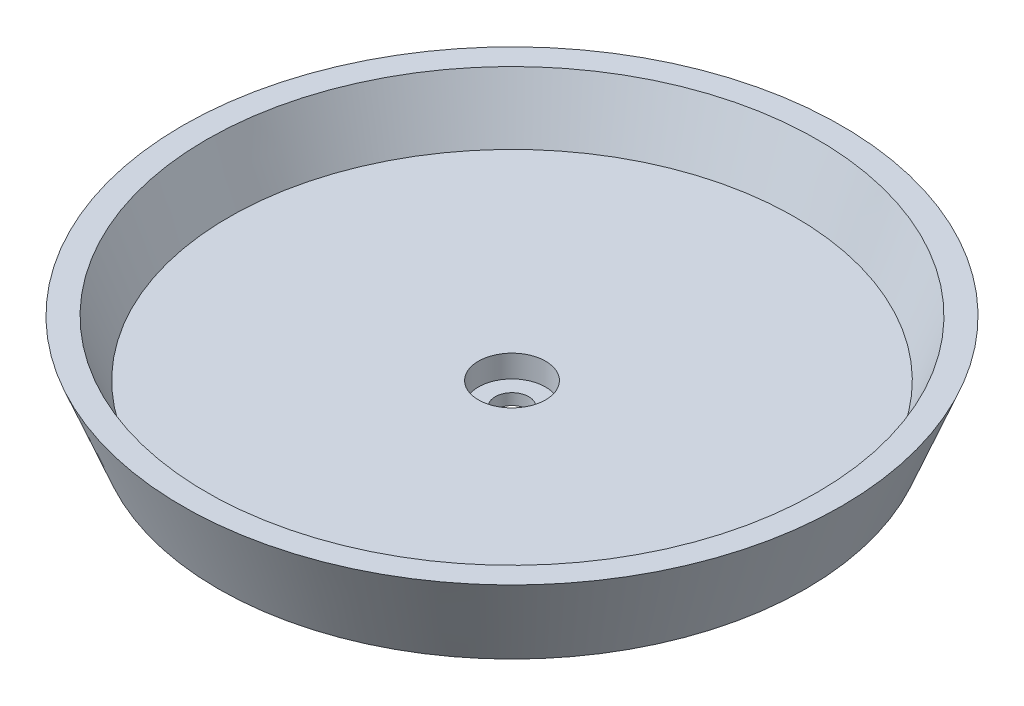
SolidWorks part; units mm, degrees
ref_plane "前视基准面" through (0, 0, 0) normal (0, 0, 1) x (1, 0, 0)
ref_plane "上视基准面" through (0, 0, 0) normal (0, 1, 0) x (1, 0, 0)
ref_plane "右视基准面" through (0, 0, 0) normal (1, 0, 0) x (0, 0, -1)
sketch "草图1" plane through (0, 0, 0) normal (0, 0, 1) x (1, 0, 0)
  line L0 (-43.8774, 13.4762) -> (-41.8774, 8.4762)
  line L1 (-41.8774, 8.4762) -> (10.7226, 8.4762)
  line L2 (-41.8774, 8.4762) -> (-41.8774, 5.4762)
  line L3 (-41.8774, 5.4762) -> (10.7226, 5.4762)
  line L4 (10.7226, 8.4762) -> (10.7226, 5.4762)
  line L5 (10.7226, 5.4762) -> (-43.8774, 5.4762)
  line L6 (10.7226, 5.4762) -> (10.7226, 13.4762)
  line L7 (10.7226, 13.4762) -> (-43.8774, 13.4762)
  line L8 (-43.8774, 5.4762) -> (-43.8774, 13.4762)
  line L9 (-46.3274, 14.2161) -> (-40.6215, -0.0487)
  line L10 (-43.8774, 13.4762) -> (-48.5334, 13.4762)
  line L11 (-46.3274, 14.2161) -> (-45.9195, 13.4762)
  line L13 (10.7226, 5.4762) -> (-16.5774, 5.4762)
  line L14 (10.7226, 5.4762) -> (10.7226, 13.4762)
  line L15 (10.7226, 13.4762) -> (-16.5774, 13.4762)
  line L16 (-16.5774, 5.4762) -> (-16.5774, 13.4762)
  line L17 (-16.5774, 8.4762) -> (-19.5774, 8.4762)
  line L18 (-16.5774, 8.4762) -> (-16.5774, 6.4762)
  line L19 (-16.5774, 6.4762) -> (-19.5774, 6.4762)
  line L20 (-19.5774, 8.4762) -> (-19.5774, 6.4762)
  line L21 (-16.5774, 5.4762) -> (-18.0774, 5.4762)
  line L22 (-16.5774, 5.4762) -> (-16.5774, 6.4762)
  line L23 (-16.5774, 6.4762) -> (-18.0774, 6.4762)
  line L24 (-18.0774, 5.4762) -> (-18.0774, 6.4762)
  dimension "D1" = 52.6
  dimension "D2" = 3
  dimension "D3" = 8
  dimension "D4" = 54.6
  dimension "D5" = 2
  dimension "D6" = 3
  dimension "D7" = 2
revolve "旋转1" add sketch "草图1" angle 360 about L16 region at (-42.958, 8.7091, 0) region at (-44.5954, 11.6811, 0) region at (-30.4664, 6.9542, 0)
